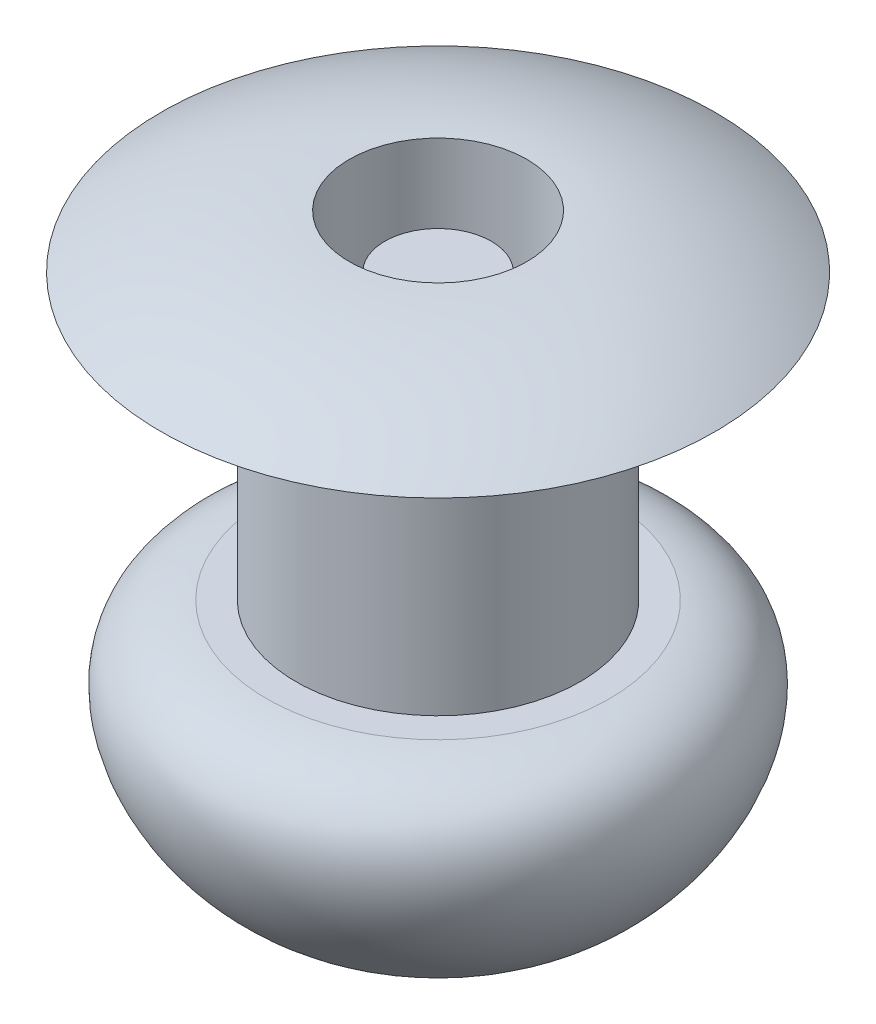
SolidWorks part; units mm, degrees
material "AISI 316 Stal nierdzewna odprężona (SS)"
ref_plane "Płaszczyzna przednia" through (0, 0, 0) normal (0, 0, 1) x (1, 0, 0)
ref_plane "Płaszczyzna górna" through (0, 0, 0) normal (0, 1, 0) x (1, 0, 0)
ref_plane "Płaszczyzna prawa" through (0, 0, 0) normal (1, 0, 0) x (0, 0, -1)
sketch "Szkic1" plane through (0, 0, 0) normal (1, 0, 0) x (0, 0, -1)
  line L0 (0, 0) -> (0, -4)
  line L1 (0, 0) -> (-0.75, 0)
  line L2 (-0.75, 0) -> (-0.75, -4)
  line L3 (-0.75, -4) -> (-1.25, -4)
  line L4 (-1.25, -4) -> (-1.25, 0.75)
  line L5 (-3.9, 0) -> (-2, 0)
  line L6 (-2, 0) -> (-2, -4)
  line L7 (-2, -4) -> (-2.4139, -4)
  line L8 (0, 0) -> (0, 0.4842) construction
  line L10 (0, -4) -> (0, -5.5)
  line L11 (-573, -4) -> (7, -4) construction
  arc A0 (-1.25, 0.75) -> (-3.9, 0) centre (-1.25, -4.3067) ccw
  ellipse E0 centre (0, -4.75) end of major axis (-1.75, -4.75) minor radius 0.75 (-0.956, -5.3782) -> (0, -5.5) ccw
  spline S0 degree 3 poles (-2.4139, -4) (-3.8586, -4.1633) (-3.5584, -6.323) (-0.9713, -7.8719) (-0.3411, -5.792) (-0.956, -5.3782) knots 0 0 0 0 0.454219 0.705201 1 1 1 1
  point P25 (-2.2069, -4)
  dimension "D1" = 7.8
  dimension "D2" = 2.5
  dimension "D3" = 4
  dimension "D4" = 0.75
  dimension "D5" = 1.5
  dimension "D6" = 1.5
  dimension "D7" = 3.5
  dimension "D8" = 3.1855
  dimension "D9" = 2.5026
  dimension "D10" = 1.9
  dimension "D11" = 1.3782
  dimension "D12" = 0.5792
  dimension "D13" = 4.8278
  dimension "D14" = 3.3858
  dimension "D15" = 2.8395
  dimension "D16" = 1.25
  dimension "D17" = 0.6409
  dimension "D18" = 0.956
revolve "Obrót1" add sketch "Szkic1" angle 360 about L8
